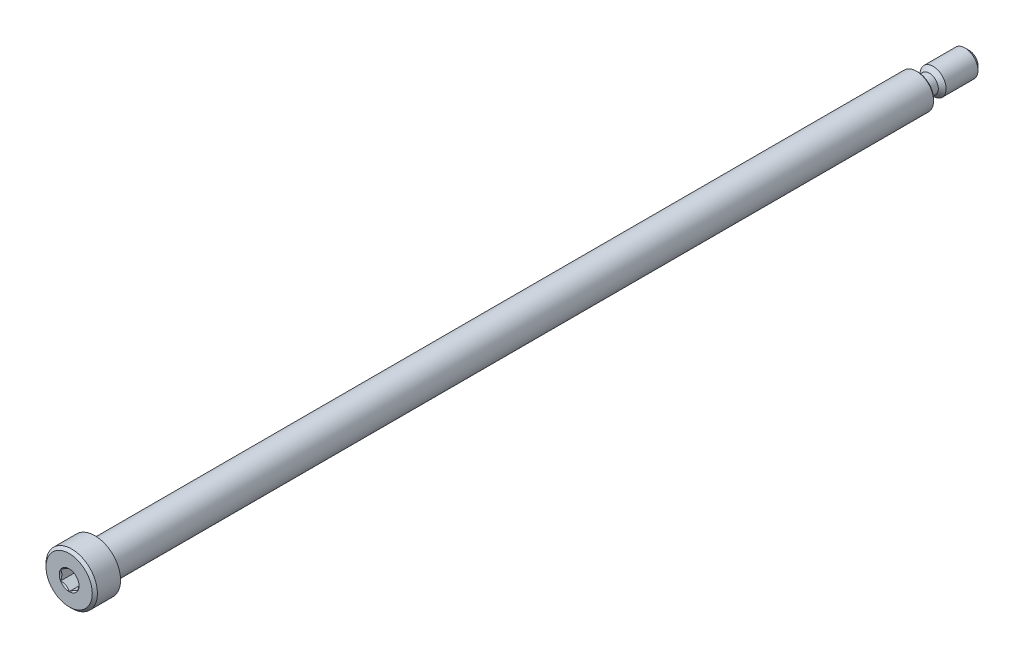
SolidWorks part; units mm, degrees
material "Alloy Steel"
ref_plane "Front Plane" through (0, 0, 0) normal (0, 0, 1) x (1, 0, 0)
ref_plane "Top Plane" through (0, 0, 0) normal (0, 1, 0) x (1, 0, 0)
ref_plane "Right Plane" through (0, 0, 0) normal (1, 0, 0) x (0, 0, -1)
sketch "Sketch2" plane through (0, 0, 0) normal (1, 0, 0) x (0, 0, -1)
  line L0 (-83.3438, 0) -> (83.3438, 0) construction
  line L1 (-83.3438, 0) -> (-83.3438, 4.7625)
  line L2 (-83.3438, 4.7625) -> (-78.5813, 4.7625)
  line L3 (-78.5813, 4.7625) -> (-78.5813, 3.175)
  line L4 (-78.5813, 3.175) -> (73.8187, 3.175)
  line L5 (73.8188, 2.413) -> (83.3438, 2.413)
  line L6 (83.3438, 2.413) -> (83.3438, 0)
  line L7 (83.2776, 2.5276) -> (83.8068, 1.611) construction
  line L8 (83.8068, 1.611) -> (84.3359, 2.5276) construction
  line L9 (84.3359, 2.5276) -> (83.2776, 2.5276) construction
  line L10 (83.3438, 2.413) -> (84.2698, 2.413) construction
  line L11 (83.8068, 2.5276) -> (83.8068, 2.413) construction
  line L12 (83.8068, 2.413) -> (83.8068, 1.7256) construction
  line L13 (83.8068, 1.7256) -> (83.8068, 1.611) construction
  line L14 (83.7406, 1.7256) -> (83.8729, 1.7256)
  line L15 (83.3107, 2.4703) -> (84.3029, 2.4703)
  line L16 (83.8729, 1.7256) -> (84.3029, 2.4703)
  line L17 (83.7406, 1.7256) -> (83.3107, 2.4703)
  line L18 (83.3438, 0) -> (83.3438, -2.413) construction
  line L19 (73.8187, -3.175) -> (73.8188, 0) construction
  line L20 (73.8188, 0) -> (73.8187, 3.175) construction
  line L21 (-83.3438, 0) -> (-83.3438, -4.7625) construction
  point P12 (80.6979, -2.413)
  point P22 (83.8068, 2.4703)
  point P23 (71.9138, 0)
  point P25 (-71.9138, 0)
  point P26 (-78.5813, -4.7625)
  point P29 (73.8187, -3.175)
  dimension "Head Height" = 4.7625
  dimension "Shoulder Diameter" = 6.35
  dimension "Screw Size Decimal Equivalent" = 4.826
  dimension "Thread Length" = 9.525
  dimension "Head Diameter" = 9.525
  dimension "Pitch" = 1.0583
  dimension "D2" = 0.1323
  dimension "D1" = 2.6458
  dimension "D3" = 11.43
  dimension "D4" = 11.43
  dimension "Shoulder Length" = 152.4
sketch "Sketch3" plane through (0, 0, 0) normal (0, 0, 1) x (1, 0, 0)
  line L1 (0, 1.8331) -> (-1.5875, 0.9165)
  line L2 (-1.5875, 0.9165) -> (-1.5875, -0.9165)
  line L3 (-1.5875, -0.9165) -> (0, -1.8331)
  line L4 (0, -1.8331) -> (1.5875, -0.9165)
  line L5 (1.5875, -0.9165) -> (1.5875, 0.9165)
  line L6 (1.5875, 0.9165) -> (0, 1.8331)
  circle A0 centre (0, 0) radius 1.5875 construction
  dimension "Drive Size" = 3.175
sketch "Sketch4" plane through (0, 0, 0) normal (1, 0, 0) x (0, 0, -1)
  line L0 (-78.5813, 4.7625) -> (-82.8675, 4.7625)
  line L1 (-82.8675, 4.7625) -> (-83.3438, 4.2862)
  line L2 (-78.5813, 4.7625) -> (-78.5813, 3.175)
  line L7 (-83.3438, 0) -> (83.3438, 0) construction
  line L8 (-78.5813, 3.175) -> (73.5648, 3.175)
  line L9 (73.5648, 3.175) -> (73.8188, 2.921)
  line L10 (73.8188, 2.921) -> (73.8188, 0)
  line L11 (73.8187, 3.175) -> (73.8188, 2.921) construction
  line L12 (73.8188, 2.921) -> (73.8188, 2.667) construction
  line L13 (73.8188, 2.667) -> (73.8188, 2.413) construction
  line L14 (-83.3438, 4.2862) -> (-83.3438, 0)
  line L16 (-83.3438, 0) -> (73.8188, 0)
  line L18 (-83.3438, 4.7625) -> (-78.5813, 4.7625) construction
  dimension "D3" = 45
  dimension "D5" = 8.5725
  dimension "D1" = 45
revolve "Revolve1" add sketch "Sketch4" angle 360 about L16
sketch "Sketch5" plane through (0, 0, 83.3438) normal (0, 0, 1) x (1, 0, 0)
  line L0 (1.5875, 0.9165) -> (0, 1.8331) construction
  line L1 (1.5875, -0.9165) -> (1.5875, 0.9165) construction
  line L2 (0, -1.8331) -> (1.5875, -0.9165) construction
  line L3 (-1.5875, -0.9165) -> (0, -1.8331) construction
  line L4 (-1.5875, 0.9165) -> (-1.5875, -0.9165) construction
  line L5 (0, 1.8331) -> (-1.5875, 0.9165) construction
  line L6 (1.5875, 0.9165) -> (0, 1.8331)
  line L7 (1.5875, -0.9165) -> (1.5875, 0.9165)
  line L8 (0, -1.8331) -> (1.5875, -0.9165)
  line L9 (-1.5875, -0.9165) -> (0, -1.8331)
  line L10 (-1.5875, 0.9165) -> (-1.5875, -0.9165)
  line L11 (0, 1.8331) -> (-1.5875, 0.9165)
extrude "Cut-Extrude1" cut sketch "Sketch5" against normal blind 3.5719
sketch "Sketch6" plane through (0, 0, 83.3438) normal (0, 0, 1) x (1, 0, 0)
  circle A0 centre (0, 0) radius 1.8331
extrude "Cut-Extrude4" cut sketch "Sketch6" against normal blind 3.5719 draft 45
sketch "Sketch7" plane through (0, 0, 0) normal (1, 0, 0) x (0, 0, -1)
  line L0 (73.8188, 2.413) -> (82.55, 2.413)
  line L1 (73.8188, 2.413) -> (83.3438, 2.413) construction
  line L2 (82.55, 2.413) -> (83.3438, 1.6192)
  line L3 (83.3438, 2.413) -> (83.3438, 0) construction
  line L4 (83.3438, 1.6192) -> (83.3438, 0)
  line L5 (83.3438, 0) -> (73.8188, 0)
  line L6 (73.8188, -2.921) -> (73.8188, 2.921) construction
  line L7 (73.8188, 0) -> (73.8188, 2.413)
  dimension "D1" = 45
  dimension "D2" = 0.7938
revolve "Revolve2" add sketch "Sketch7" angle 360 about L5
sketch "Sketch10" plane through (0, 0, 0) normal (1, 0, 0) x (0, 0, -1)
  line L0 (74.5426, 1.6891) -> (75.927, 1.6891)
  line L1 (75.927, 1.6891) -> (77.4129, 3.175)
  line L2 (77.4129, 3.175) -> (73.8187, 3.175)
  line L3 (73.8187, 3.175) -> (73.8188, 2.413)
  line L4 (73.8188, -2.921) -> (73.8188, 2.921) construction
  line L5 (83.3438, 0) -> (73.8188, 0) construction
  line L6 (-83.3438, 0) -> (83.3438, 0) construction
  arc A0 (73.8188, 2.413) -> (74.5426, 1.6891) centre (74.5427, 2.413) ccw
  dimension "Flat OD" = 3.3782
  dimension "Flat" = 2.1082
  dimension "D3" = 45
revolve "Cut-Revolve1" cut sketch "Sketch10" angle 360 about L5
sketch "Sketch8" [suppressed] plane through (0, 0, -83.3438) normal (0, 0, -1) x (-1, 0, 0)
  circle A0 centre (0, 0) radius 2.413 construction
  circle A1 centre (0, 0) radius 2.413
curve "Helix/Spiral1" [suppressed] pitch 1.0583 height 10.5833 turns 10
sketch "Sketch9" [suppressed] plane through (0, 0, 0) normal (1, 0, 0) x (0, 0, -1)
  line L0 (83.7406, 1.7256) -> (83.8729, 1.7256) construction
  line L1 (83.8729, 1.7256) -> (84.3029, 2.4703) construction
  line L2 (83.3107, 2.4703) -> (84.3029, 2.4703) construction
  line L3 (83.7406, 1.7256) -> (83.3107, 2.4703) construction
  line L4 (83.7406, 1.7256) -> (83.8729, 1.7256)
  line L5 (83.8729, 1.7256) -> (84.3029, 2.4703)
  line L6 (83.3107, 2.4703) -> (84.3029, 2.4703)
  line L7 (83.7406, 1.7256) -> (83.3107, 2.4703)
ref_plane "Plane1" [suppressed] through (0, 0, -75.927) normal (0, 0, 1) x (1, 0, 0)
split "Split1" [suppressed] bodies to split 138
sweep "Cut-Sweep1" [suppressed] cut profiles "Sketch9" path "Helix/Spiral1"
combine bodies "Combine1" [suppressed] operation type add bodies to combine 141 139
sketch "Sketch11" [suppressed] plane through (0, 0, 83.3438) normal (0, 0, 1) x (1, 0, 0)
  line L0 (-0.0687, 4.7625) -> (0.0687, 4.7625)
  line L1 (0.0687, 4.7625) -> (0, 4.6434)
  line L2 (0, 0) -> (0, 4.7625) construction
  line L3 (0, 4.6434) -> (-0.0687, 4.7625)
  line L4 (0, 0) -> (4.7625, 0) construction
  circle A0 centre (0, 0) radius 4.7625 construction
  point P6 (0, 4.7625)
  dimension "D1" = 9.2869
  dimension "D2" = 60
  dimension "D3" = 0.1375
sketch "Sketch12" [suppressed] plane through (0, 0, 0) normal (1, 0, 0) x (0, 0, -1)
  line L0 (-83.3438, 4.6434) -> (-80.0593, 4.6434)
  line L1 (-79.6528, 5.0499) -> (-79.6528, 4.7625) construction
  line L2 (-83.3438, 4.7625) -> (-78.5813, 4.7625) construction
  arc A0 (-80.0593, 4.6434) -> (-79.6528, 5.0499) centre (-80.0593, 5.0499) ccw
  point P11 (-79.7719, 4.7625)
  dimension "D1" = 1.1906
sweep "Cut-Sweep2" [suppressed] cut profiles "Sketch11" path "Sketch12"
pattern_circular "CirPattern1" [suppressed] count 76 over 360 about axis through (0, 0, 83.3438) along (0, 0, -1) of bodies 143
equation "\"D2@Sketch2\" = \"Pitch@Sketch2\" / 8"
equation "\"D1@Sketch2\"=\"Pitch@Sketch2\"*2.5"
equation "\"D5@Sketch4\"=\"Head Diameter@Sketch2\"*0.9"
equation "\"D1@Cut-Extrude1\"=\"Head Height@Sketch2\"*0.75"
equation "\"D1@Cut-Extrude4\"=\"D1@Cut-Extrude1\""
equation "\"D2@Sketch7\"=\"pitch@sketch2\"*0.75"
equation "\"D3@Helix/Spiral1\"=\"Thread Length@Sketch2\"+\"Pitch@Sketch2\""
equation "\"D4@Helix/Spiral1\"=\"Pitch@Sketch2\""
equation "\"D1@Sketch11\"=\"Head Diameter@Sketch2\"*0.975"
equation "\"D1@Sketch12\"=\"Head Height@Sketch2\"*0.25"
equation "\"D1@CirPattern1\"=\"Head Diameter@Sketch2\" * 3.14 / \"D3@Sketch11\" * 0.35"
equation "\"D3@Sketch2\"=\"Thread Length@Sketch2\"*1.2"
equation "\"D4@Sketch2\"=\"D3@Sketch2\""
